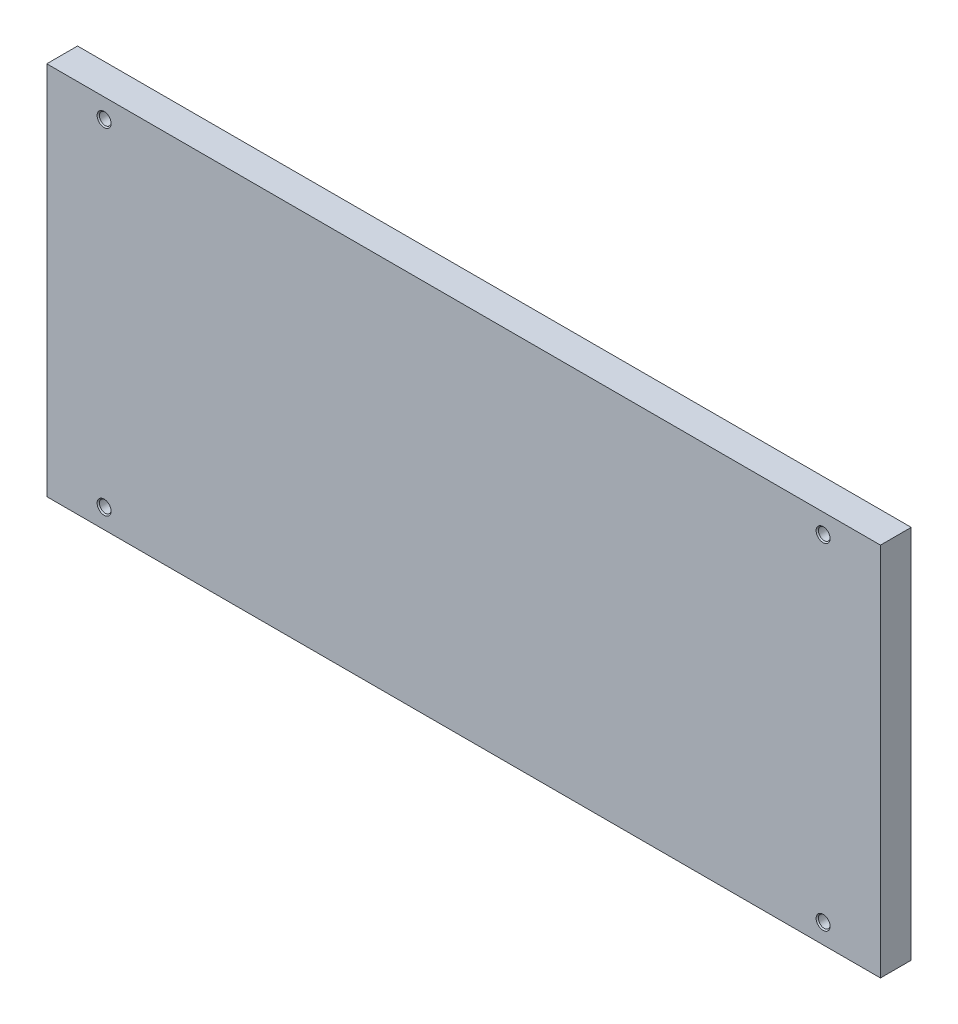
SolidWorks part; units mm, degrees
ref_plane "Płaszczyzna przednia" through (0, 0, 0) normal (0, 0, 1) x (1, 0, 0)
ref_plane "Płaszczyzna górna" through (0, 0, 0) normal (0, 1, 0) x (1, 0, 0)
ref_plane "Płaszczyzna prawa" through (0, 0, 0) normal (1, 0, 0) x (0, 0, -1)
sketch "Szkic1" plane through (0, 0, 0) normal (0, 0, 1) x (1, 0, 0)
  line L0 (-298, -134) -> (298, -134)
  line L1 (298, -134) -> (298, 134)
  line L2 (298, 134) -> (-298, 134)
  line L3 (-298, 134) -> (-298, -134)
extrude "Dodanie-wyciągnięcie1" add sketch "Szkic1" along normal blind 22
ref_plane "Płaszczyzna1" through (257, 0, 0) normal (1, 0, 0) x (0, 0, -1)
ref_plane "Płaszczyzna2" through (-257, 0, 0) normal (1, 0, 0) x (0, 0, -1)
sketch "Szkic2" plane through (-257, 0, 0) normal (1, 0, 0) x (0, 0, -1)
  line L0 (-22, 120) -> (-22, 125)
  line L1 (-22, 125) -> (-21.188, 124.188)
  line L2 (-21.188, 124.188) -> (-0.812, 124.188)
  line L3 (-0.812, 124.188) -> (0, 125)
  line L4 (0, 125) -> (0, 120)
  line L5 (0, 120) -> (-22, 120)
  line L6 (0, 120) -> (-22, 120) construction
revolve "Wycięcie-obrót1" cut sketch "Szkic2" angle 360 about L6 reverse direction yes
cosmetic thread "Oznaczenie gwintu1" parameters "D1"=22, "D2"=10
sketch "Szkic3" plane through (-257, 0, 0) normal (1, 0, 0) x (0, 0, -1)
  line L0 (0, -120) -> (0, -125)
  line L1 (0, -125) -> (-0.812, -124.188)
  line L2 (-0.812, -124.188) -> (-21.188, -124.188)
  line L3 (-21.188, -124.188) -> (-22, -125)
  line L4 (-22, -125) -> (-22, -120)
  line L5 (-22, -120) -> (0, -120)
  line L6 (-22, -120) -> (0, -120) construction
revolve "Wycięcie-obrót2" cut sketch "Szkic3" angle 360 about L6 reverse direction yes
cosmetic thread "Oznaczenie gwintu2" parameters "D1"=22, "D2"=10
sketch "Szkic4" plane through (257, 0, 0) normal (1, 0, 0) x (0, 0, -1)
  line L0 (-22, 120) -> (-22, 125)
  line L1 (-22, 125) -> (-21.188, 124.188)
  line L2 (-21.188, 124.188) -> (-0.812, 124.188)
  line L3 (-0.812, 124.188) -> (0, 125)
  line L4 (0, 125) -> (0, 120)
  line L5 (0, 120) -> (-22, 120)
  line L6 (0, 120) -> (-22, 120) construction
revolve "Wycięcie-obrót3" cut sketch "Szkic4" angle 360 about L6 reverse direction yes
cosmetic thread "Oznaczenie gwintu3" parameters "D1"=22, "D2"=10
sketch "Szkic5" plane through (257, 0, 0) normal (1, 0, 0) x (0, 0, -1)
  line L0 (0, -120) -> (0, -125)
  line L1 (0, -125) -> (-0.812, -124.188)
  line L2 (-0.812, -124.188) -> (-21.188, -124.188)
  line L3 (-21.188, -124.188) -> (-22, -125)
  line L4 (-22, -125) -> (-22, -120)
  line L5 (-22, -120) -> (0, -120)
  line L6 (-22, -120) -> (0, -120) construction
revolve "Wycięcie-obrót4" cut sketch "Szkic5" angle 360 about L6 reverse direction yes
cosmetic thread "Oznaczenie gwintu4" parameters "D1"=22, "D2"=10
ref_plane "IP1 XY" through (0, 0, 0) normal (0, 0, 1) x (1, 0, 0)
ref_plane "IP1 XZ" through (0, 0, 0) normal (0, -1, 0) x (-1, 0, 0)
ref_plane "IP1 YZ" through (0, 0, 0) normal (1, 0, 0) x (0, 0, -1)
ref_axis "IP1 X" through (-80.9, 0, 0) along (1, 0, 0)
ref_axis "IP1 Y" through (0, -50, 0) along (0, 1, 0)
ref_axis "IP1 Z" through (0, 0, 80.9) along (0, 0, -1)
sketch3d "IP1"
  point P0 (0, 0, 0)
